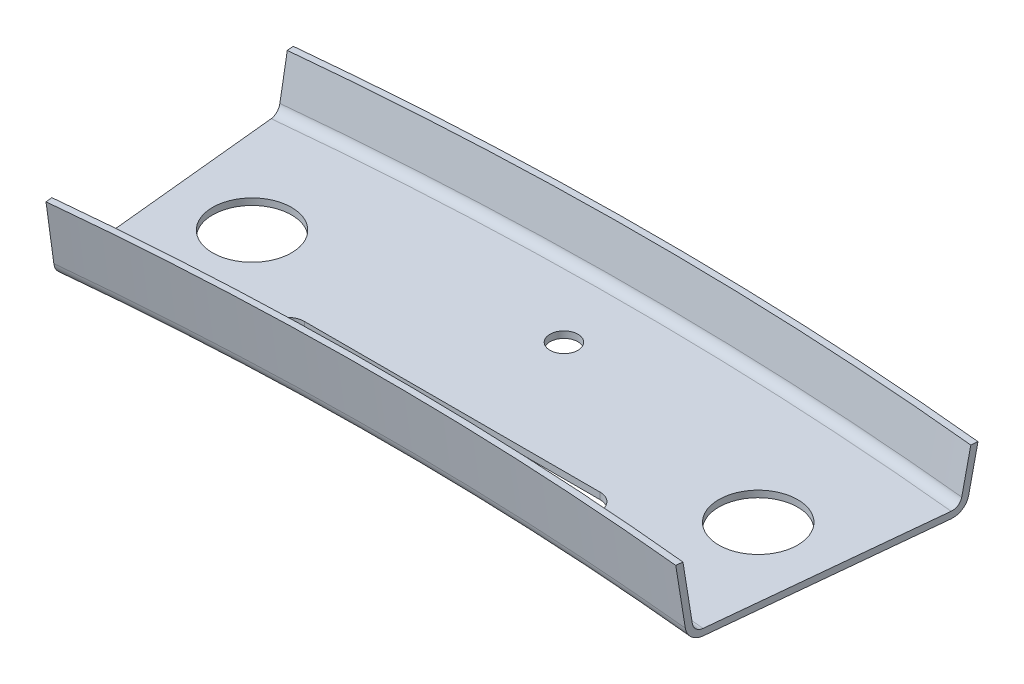
SolidWorks part; units mm, degrees
ref_plane "Front Plane" through (0, 0, 0) normal (0, 0, 1) x (1, 0, 0)
ref_plane "Top Plane" through (0, 0, 0) normal (0, 1, 0) x (1, 0, 0)
ref_plane "Right Plane" through (0, 0, 0) normal (1, 0, 0) x (0, 0, -1)
sketch "Sketch1" plane through (0, 0, 0) normal (0, 1, 0) x (1, 0, 0)
  arc A0 (-100, -5) -> (100, -5) centre (0, -1002.5) cw
  point P3 (0, 0)
  dimension "D1" = 5
  dimension "D2" = 200
sketch "Sketch2" plane through (0, 0, 0) normal (1, 0, 0) x (0, 0, -1)
  line L0 (-34.4785, 0) -> (34.4785, 0)
  line L2 (37.4203, 2.4117) -> (39.9379, 15)
  line L3 (39.9379, 15) -> (41.9379, 15)
  line L4 (41.9379, 15) -> (39.3418, 2.0194)
  line L5 (34.4389, -2) -> (-34.4561, -2)
  line L6 (-39.4008, 2.2583) -> (-42.0621, 20)
  line L7 (-42.0621, 20) -> (-40.0621, 20)
  line L9 (-40.0621, 20) -> (-37.4453, 2.555)
  arc A1 (-34.4785, 0) -> (-37.4453, 2.555) centre (-34.4785, 3) cw
  arc A2 (-34.4561, -2) -> (-39.4008, 2.2583) centre (-34.4561, 3) cw
  arc A3 (39.3418, 2.0194) -> (34.4389, -2) centre (34.4389, 3) cw
  arc A4 (37.4203, 2.4117) -> (34.4785, 0) centre (34.4785, 3) cw
  point P1 (35.5909, 0)
  point P3 (-37.0621, 0)
  point P11 (0, 0)
  point P14 (36.9379, 0)
  point P18 (43.0031, 15)
  point P19 (35.1911, 0)
  point P23 (36.9379, 0)
  dimension "D6" = 3
  dimension "D8" = 3
  dimension "D9" = 5
  dimension "D10" = 5
  dimension "D11" = 3
  dimension "D1" = 17
  dimension "D2" = 80
  dimension "D3" = 3
  dimension "D4" = 2
  dimension "D5" = 2
  dimension "D7" = 22
sweep "Sweep1" add profiles "Sketch2" path "Sketch1"
sketch "Sketch3" plane through (0, 0, 0) normal (0, 1, 0) x (1, 0, 0)
  circle A0 centre (0, 14.9379) radius 4.25
  circle A2 centre (-77, -2.9615) radius 12
  circle A3 centre (77, -2.9615) radius 12
  arc A4 (-77, -2.9615) -> (77, -2.9615) centre (0, -1002.5) cw construction
  arc A5 (95.8043, -46.8523) -> (-95.8043, -46.8523) centre (0, -1002.5) ccw construction
  arc A6 (103.9838, 34.7387) -> (-103.9838, 34.7387) centre (0, -1002.5) ccw construction
  point P8 (0, 39.9379)
  point P12 (0, 0)
  dimension "D1" = 8.5
  dimension "D3" = 24
  dimension "D2" = 25
  dimension "D4" = 154
extrude "Mounting points" cut sketch "Sketch3" against normal through all both and the other way through all
sketch "Sketch4" plane through (0, 0, 0) normal (0, 1, 0) x (1, 0, 0)
  line L0 (-45, -24.0621) -> (45, -24.0621) construction
  line L1 (-45, -19.0621) -> (45, -19.0621)
  line L2 (-45, -29.0621) -> (45, -29.0621)
  arc A0 (-45, -19.0621) -> (-45, -29.0621) centre (-45, -24.0621) ccw
  arc A1 (45, -29.0621) -> (45, -19.0621) centre (45, -24.0621) ccw
  circle A3 centre (0, 14.9379) radius 4.25 construction
  point P2 (0, -24.0621)
  dimension "D1" = 5
  dimension "D2" = 90
  dimension "D3" = 34
extrude "Slot clearance" cut sketch "Sketch4" against normal through all both and the other way through all
